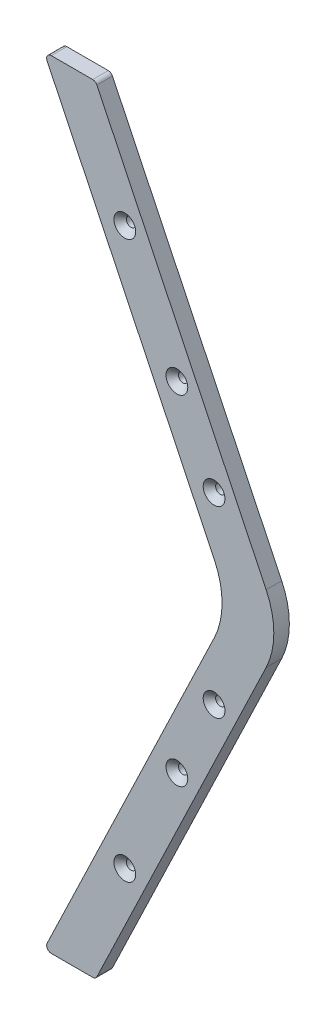
SolidWorks part; units mm, degrees
ref_plane "Ön Düzlem" through (0, 0, 0) normal (0, 0, 1) x (1, 0, 0)
ref_plane "Üst Düzlem" through (0, 0, 0) normal (0, 1, 0) x (1, 0, 0)
ref_plane "Sağ Düzlem" through (0, 0, 0) normal (1, 0, 0) x (0, 0, -1)
sketch "Çizim1" plane through (0, 0, 0) normal (0, 0, 1) x (1, 0, 0)
  line L3 (100.428, 0) -> (-19.6172, 250)
  line L8 (2.0549, 204.7052) -> (89.6744, 21.5804) construction
  line L9 (100.428, 0) -> (-19.6172, -250)
  line L10 (89.6744, -21.5804) -> (2.0549, -204.7052) construction
  line L12 (133.7074, 0) -> (13.6621, 250)
  line L14 (13.6621, -250) -> (133.7074, 0)
  line L16 (-19.6172, -250) -> (13.6621, -250)
  line L17 (0, 0) -> (100.428, 0) construction
  line L18 (-19.6172, 250) -> (13.6621, 250)
  point P0 (73.6848, -125)
  dimension "D1" = 30
  dimension "D2" = 250
  dimension "D4" = 30
  dimension "D3" = 250
  dimension "D5" = 128.701
extrude "Yükseklik-Ekstrüzyon1" add sketch "Çizim1" along normal blind 10
fillet "Radyus1" radius 3 4 edges at (-19.6172, -250, 5) (13.6621, -250, 5) (-19.6172, 250, 5) (13.6621, 250, 5)
fillet "Radyus2" radius 50 2 edges at (133.7074, 0, 5) (100.428, 0, 5)
sketch "Çizim2" plane through (0, 0, 10) normal (0, 0, 1) x (1, 0, 0)
  circle A0 centre (32.4181, -179) radius 3
  circle A1 centre (65.9109, -109) radius 3
  circle A2 centre (89.8343, -59) radius 3
  circle A3 centre (65.9109, 109) radius 3
  circle A4 centre (89.8343, 59) radius 3
  circle A5 centre (32.4181, 179) radius 3
  dimension "D1" = 6
extrude "Kes-Ekstrüzyon1" cut sketch "Çizim2" against normal blind 68
chamfer "Pah1" distance 4 angle 45 6 edges at (35.4181, -179, 10) (68.9109, -109, 10) (92.8343, -59, 10) (92.8343, 59, 10) (68.9109, 109, 10) (35.4181, 179, 10)
sketch "Çizim3" plane through (0, 0, 0) normal (0, 0, 1) x (1, 0, 0)
  line L1 (-59.926, 0) -> (200.9484, 0)
  line L2 (-59.926, 0) -> (-59.926, -365.2036)
  line L3 (-59.926, -365.2036) -> (200.9484, -365.2036)
  line L4 (200.9484, 0) -> (200.9484, -365.2036)
extrude "Kes-Ekstrüzyon6" [suppressed] cut sketch "Çizim3" against normal blind 154 and the other way blind 10
